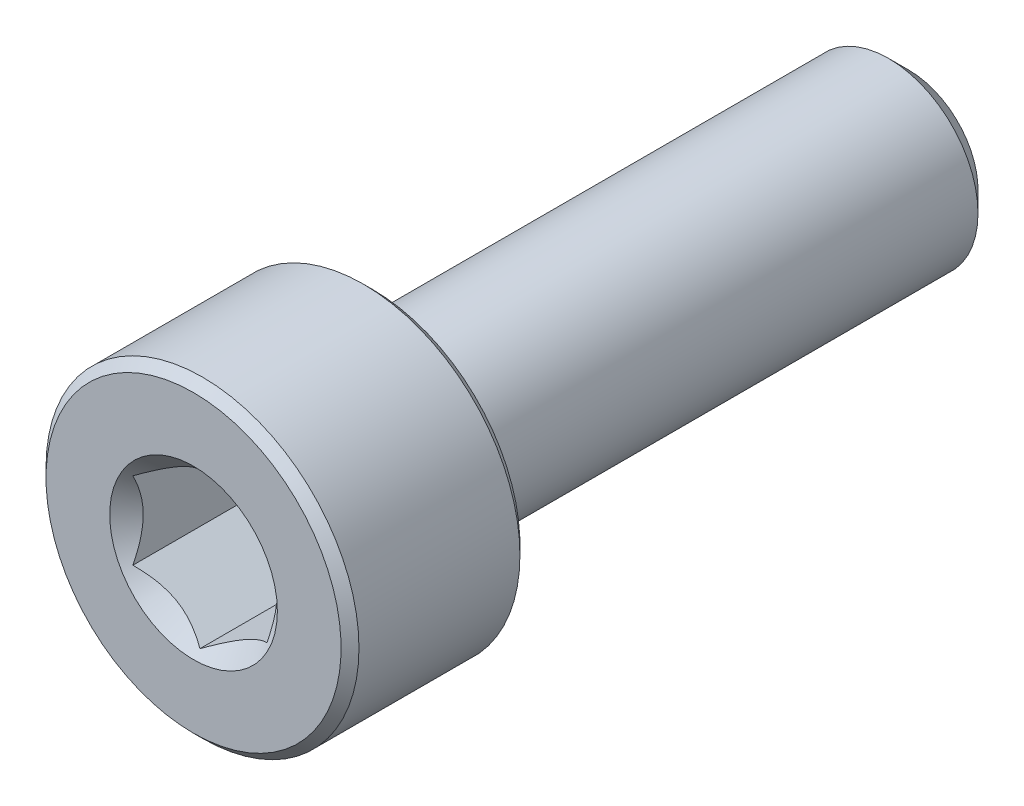
SolidWorks part; units mm, degrees
ref_plane "Front Plane" through (0, 0, 0) normal (0, 0, 1) x (1, 0, 0)
ref_plane "Top Plane" through (0, 0, 0) normal (0, 1, 0) x (1, 0, 0)
ref_plane "Right Plane" through (0, 0, 0) normal (1, 0, 0) x (0, 0, -1)
sketch "Sketch1" plane through (0, 0, 0) normal (1, 0, 0) x (0, 0, -1)
  line L0 (-8, 0) -> (8, 0) construction
  line L1 (8, 0) -> (8, 1.5453) construction
  line L2 (8, 1.5453) -> (7.5453, 2) construction
  line L3 (7.5453, 2) -> (7.475, 2) construction
  line L4 (7.475, 2) -> (-4, 2) construction
  line L5 (-4, 2) -> (-4, 3.5) construction
  line L6 (-4, 3.5) -> (-8, 3.5) construction
  line L7 (-8, 3.5) -> (-8, 0) construction
  line L8 (8, 1.5453) -> (8, 2) construction
  line L9 (7.9562, 2.0758) -> (8.3062, 1.4696) construction
  line L10 (8.3062, 1.4696) -> (8.6562, 2.0758) construction
  line L11 (8.6562, 2.0758) -> (7.9562, 2.0758) construction
  line L12 (8.3062, 2.0758) -> (8.3062, 2) construction
  line L13 (8.3062, 1.4696) -> (8.3062, 1.5453) construction
  line L14 (8.2625, 1.5453) -> (8.35, 1.5453) construction
  line L15 (8, 2) -> (8.6125, 2) construction
  line L16 (7.9781, 2.0379) -> (8.6344, 2.0379) construction
  line L17 (8, 0) -> (8, -2) construction
  line L18 (-4.2, 3.5) -> (-4, 3.3) construction
  line L19 (-7.8, 3.5) -> (-8, 3.3) construction
  line L20 (-4, 2) -> (-4, 0) construction
  line L21 (-4, 1) -> (0, 1) construction
  line L22 (0, 1) -> (4, 1) construction
  line L23 (4, 1) -> (8, 1) construction
  line L24 (0, 1) -> (0, 2) construction
  line L25 (0, 2) -> (0, 3.5) construction
  line L26 (4, 1) -> (4, 3.5) construction
  point P0 (-8, 1.5)
  point P3 (6.25, 2)
  point P4 (0, 0)
  point P18 (4, 2)
  point P22 (8.3062, 1.5453)
  point P24 (7.475, 2)
  point P25 (8.3062, 2)
  point P28 (8.3062, 2.0379)
  point P29 (6.25, -2)
  point P30 (0, 2)
  point P31 (-6, 3.5)
  point P37 (-4.7, 3.5)
  point P38 (-7.7, 3.5)
  point P45 (0, 1)
  point P46 (4, 1)
  dimension "D2" = 0.0875
  dimension "D7" = 0.2
  dimension "D8" = 0.2
  dimension "D9" = 0.2
  dimension "D10" = 0.1
  dimension "D11" = 0.5
  dimension "Drive Size" = 3
  dimension "Head Diameter" = 7
  dimension "Head Height" = 4
  dimension "Thread Pitch" = 0.7
  dimension "Thread Size" = 4
  dimension "Length" = 12
  dimension "D12" = 0.525
  dimension "D4" = 1.75
  dimension "D3" = 45
sketch "Sketch2" plane through (0, 0, 0) normal (1, 0, 0) x (0, 0, -1)
  line L0 (-8, 0) -> (-8, 3.3)
  line L1 (-7.8, 3.5) -> (-4.2, 3.5)
  line L2 (-4, 3.3) -> (-4, 2.2)
  line L4 (7.5453, 2) -> (8, 1.5453)
  line L5 (8, 1.5453) -> (8, 0)
  line L6 (-4, 3.5) -> (-8, 3.5) construction
  line L7 (8, 0) -> (-8, 0)
  line L8 (-7.8, 3.5) -> (-8, 3.3) construction
  line L10 (-7.8, 3.5) -> (-8, 3.3)
  line L14 (-4.2, 3.5) -> (-4, 3.3) construction
  line L16 (-4.2, 3.5) -> (-4, 3.3)
  line L17 (-4, 2) -> (-4, 3.5) construction
  line L19 (-3.8, 2) -> (7.5453, 2)
  line L20 (7.475, 2) -> (-4, 2) construction
  arc A1 (-4, 2.2) -> (-3.8, 2) centre (-3.8, 2.2) ccw
  dimension "D3" = 0.2
revolve "Revolve1" add sketch "Sketch2" angle 360 about L7
sketch "Sketch3" plane through (0, 0, 8) normal (0, 0, 1) x (1, 0, 0)
  line L1 (1.5, -0.866) -> (1.5, 0.866)
  line L2 (1.5, 0.866) -> (0, 1.7321)
  line L3 (0, 1.7321) -> (-1.5, 0.866)
  line L4 (-1.5, 0.866) -> (-1.5, -0.866)
  line L5 (-1.5, -0.866) -> (0, -1.7321)
  line L6 (0, -1.7321) -> (1.5, -0.866)
  circle A0 centre (0, 0) radius 1.5 construction
  circle A1 centre (0, 0) radius 3.5 construction
  circle A2 centre (0, 0) radius 3.5 construction
  circle A3 centre (0, 0) radius 1.7321 construction
  point P13 (0, 0)
extrude "Cut-Extrude1" cut sketch "Sketch3" against normal offset from surface (3 mm away) 1 up to face at (0, 3.3, 4)
sketch "Sketch4" plane through (0, 0, 8) normal (0, 0, 1) x (1, 0, 0)
  circle A0 centre (0, 0) radius 1.875
  dimension "D1" = 3.75
extrude "Cut-Extrude2" cut sketch "Sketch4" against normal up to vertex (2 mm away) draft 45 up to point (0, 3.5, 6)
sketch "Sketch11" plane through (0, 0, 0) normal (1, 0, 0) x (0, 0, -1)
  line L0 (-8, 0) -> (8, 0) construction
  line L1 (-8, 0) -> (8, 0) construction
  line L2 (-1.75, 0) -> (-1.75, 2) construction
  line L3 (7.475, 2) -> (-4, 2) construction
  line L4 (5.75, 0) -> (5.75, 2) construction
  line L6 (8, 1.5453) -> (8, 2) construction
  point P2 (-1.75, 0)
  point P3 (5.75, 0)
  dimension "D1" = 2.25
  dimension "D2" = 2.25
sketch "Sketch6" [suppressed] plane through (0, 0, -8) normal (0, 0, -1) x (-1, 0, 0)
  circle A0 centre (0, 0) radius 2
curve "Helix/Spiral1" [suppressed] pitch 0.7 height 12.7 turns 18.1429
sketch "Sketch10" [suppressed] plane through (0, 0, 0) normal (1, 0, 0) x (0, 0, -1)
  line L0 (-3.8, -3.5) -> (-3.8, 3.5)
  line L5 (-8, 0) -> (8, 0) construction
  line L6 (-3.8, 2) -> (-3.8, -2) construction
  point P3 (-3.8, 0)
split "Split1" [suppressed] bodies to split 106
sketch "Sketch7" [suppressed] plane through (0, 0, 0) normal (1, 0, 0) x (0, 0, -1)
  line L0 (7.9781, 2.0379) -> (8.6344, 2.0379)
  line L1 (8.6344, 2.0379) -> (8.35, 1.5453)
  line L2 (8.35, 1.5453) -> (8.2625, 1.5453)
  line L3 (8.2625, 1.5453) -> (7.9781, 2.0379)
sweep "Cut-Sweep1" [suppressed] cut profiles "Sketch7" path "Helix/Spiral1"
sketch "Sketch8" [suppressed] plane through (0, 0, 0) normal (1, 0, 0) x (0, 0, -1)
  line L0 (-4, 0) -> (-4, 2)
  line L1 (-3.8, -2) -> (-3.8, 2) construction
  line L2 (-4, 2) -> (-3.8, 2)
  line L4 (-3.8, 2) -> (-2.6453, 0)
  line L5 (-2.6453, 0) -> (-4, 0)
  line L6 (7.475, 2) -> (-4, 2) construction
  line L7 (-8, 0) -> (8, 0) construction
  dimension "D1" = 60
revolve "Revolve2" [suppressed] add sketch "Sketch8" angle 360 about L5
ref_plane "Plane1" [suppressed] through (0, 0, 8) normal (0, 0, 1) x (1, 0, 0)
sketch "Sketch12" [suppressed] plane through (0, 0, 8) normal (0, 0, 1) x (1, 0, 0)
  line L0 (0, 0) -> (0.1221, 3.4979) construction
  line L1 (0, 0) -> (-0.1221, 3.4979) construction
  line L2 (0, 3.4125) -> (0, 3.5875) construction
  line L3 (-0.2118, 3.5875) -> (0.2118, 3.5875)
  line L4 (-0.2118, 3.5875) -> (-0.0628, 3.4385)
  line L5 (0.0628, 3.4385) -> (0.2118, 3.5875)
  circle A0 centre (0, 0) radius 3.5 construction
  arc A1 (-0.0628, 3.4385) -> (0.0628, 3.4385) centre (0, 3.5013) ccw
  point P9 (0, 3.5875)
  point P13 (0, 3.5)
  dimension "D1" = 4
  dimension "D2" = 0.0875
extrude "Cut-Extrude3" [suppressed] cut sketch "Sketch12" against normal blind 3.2
pattern_circular "CirPattern1" [suppressed] count 72 over 360 about axis through (0, 0, 8) along (0, 0, -1) of bodies 118
ref_axis "Z" through (0, 0, -8.8015) along (0, 0, 1)
equation "\"D2@Sketch1\" = \"Thread Pitch@Sketch1\" / 8"
equation "\"D4@Helix/Spiral1\" = \"Thread Pitch@Sketch1\""
equation "\"D7@Sketch1\" = \"Head Height@Sketch1\" * .05"
equation "\"D8@Sketch1\"=\"D7@Sketch1\""
equation "\"D9@Sketch1\"=\"D7@Sketch1\""
equation "\"D10@Sketch1\"=\"D7@Sketch1\"/2"
equation "\"D11@Sketch1\"=\"D10@Sketch1\"*5"
equation "\"D4@Sketch1\"=\"Thread Pitch@Sketch1\"*2.5"
equation "\"D12@Sketch1\"=\"Thread Pitch@Sketch1\"*.75"
equation "\"D3@Helix/Spiral1\"=\"Length@Sketch1\"+\"Thread Pitch@Sketch1\""
equation "\"D3@Sketch2\" = \"Thread Size@Sketch1\" * 0.05"
equation "\"D1@Sketch11\"=\"Length@Sketch1\"*0.1875"
equation "\"D2@Sketch11\"=\"D1@Sketch11\""
equation "\"D2@Sketch12\"=\"Head Diameter@Sketch1\"*.0125"
equation "\"D1@Cut-Extrude3\"=\"Head Height@Sketch1\"*.8"
equation "\"D1@CirPattern1\"=\"D3@CirPattern1\"/(1.25*\"D1@Sketch12\")"
equation "\"D1@Sketch4\"=\"Drive Size@Sketch1\"*1.25"
